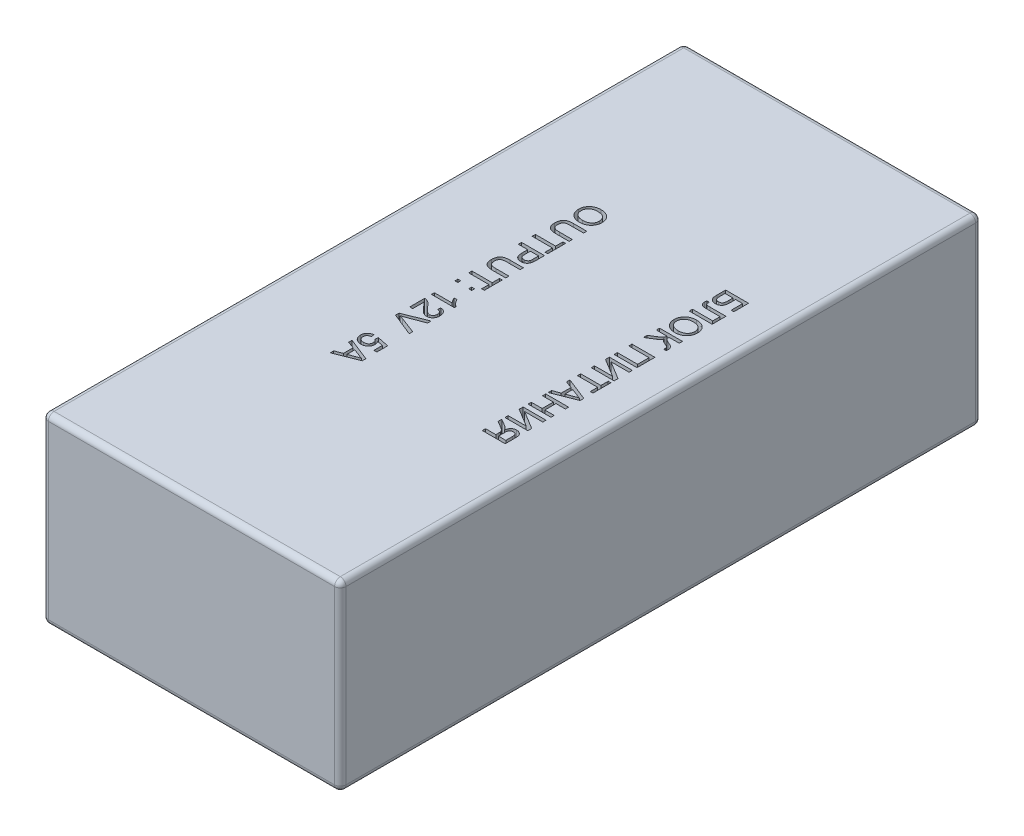
SolidWorks part; units mm, degrees
ref_plane "Спереди" through (0, 0, 0) normal (0, 0, 1) x (1, 0, 0)
ref_plane "Сверху" through (0, 0, 0) normal (0, 1, 0) x (1, 0, 0)
ref_plane "Справа" through (0, 0, 0) normal (1, 0, 0) x (0, 0, -1)
sketch "Эскиз1" plane through (0, 0, 0) normal (0, 0, 1) x (1, 0, 0)
  line L1 (-26, 16) -> (26, 16)
  line L2 (-26, 16) -> (-26, -16)
  line L3 (-26, -16) -> (26, -16)
  line L4 (26, 16) -> (26, -16)
  line L5 (-26, 16) -> (26, -16) construction
  line L6 (-26, -16) -> (26, 16) construction
  point P0 (0, 0)
  dimension "D1" = 32
  dimension "D2" = 52
extrude "Бобышка-Вытянуть1" add sketch "Эскиз1" against normal blind 112
fillet "Скругление1" radius 1 11 edges at (-26, 0, -112) (0, 16, -112) (0, -16, -112) (26, 0, -112) (26, -16, -56) (26, 0, 0) (-26, 0, 0) (0, -16, 0) (-26, 16, -56) (0, 16, 0) (26, 16, -56)
fillet "Скругление2" radius 1 3 edges at (-25.7071, -15.7071, -111.7071) (-25.7071, -15.7071, -0.2929) (-26, -16, -56)
sketch "Эскиз2" plane through (0, 16, 0) normal (0, 1, 0) x (1, 0, 0)
  text T0 "БЛОК ПИТАНИЯ"
  text T1 "OUTPUT: 12V  5A"
extrude "Вырез-Вытянуть4" cut sketch "Эскиз2" against normal blind 5
